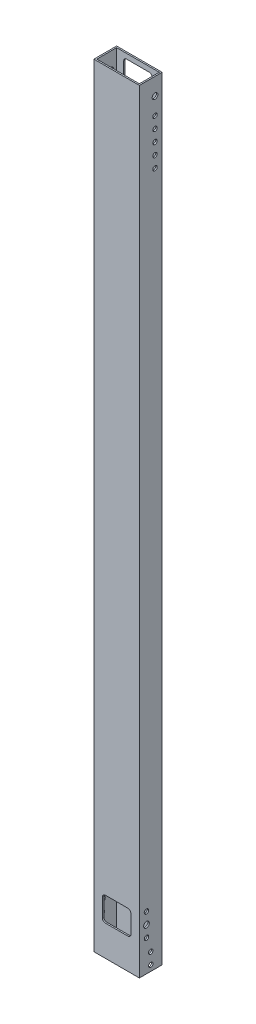
SolidWorks part; units mm, degrees
material "6061-T6 (SS)"
ref_plane "Front Plane" through (0, 0, 0) normal (0, 0, 1) x (1, 0, 0)
ref_plane "Top Plane" through (0, 0, 0) normal (0, 1, 0) x (1, 0, 0)
ref_plane "Right Plane" through (0, 0, 0) normal (1, 0, 0) x (0, 0, -1)
sketch "Sketch1" plane through (0, 0, 0) normal (0, 0, 1) x (1, 0, 0)
  line L1 (-25.4, -431.8) -> (25.4, -431.8)
  line L2 (-25.4, -431.8) -> (-25.4, 431.8)
  line L3 (-25.4, 431.8) -> (25.4, 431.8)
  line L4 (25.4, -431.8) -> (25.4, 431.8)
  line L5 (-25.4, -431.8) -> (25.4, 431.8) construction
  line L6 (-25.4, 431.8) -> (25.4, -431.8) construction
  point P0 (0, 0)
  dimension "D1" = 50.8
  dimension "D2" = 863.6
extrude "Boss-Extrude1" add sketch "Sketch1" along normal mid plane 25.4
shell "Shell1" thickness 1.5875 removed face at (0, -431.8, 0) removed face at (0, 431.8, 0)
sketch "Sketch3" plane through (0, 0, 0) normal (1, 0, 0) x (0, 0, -1)
  line L0 (-12.7, -431.8) -> (12.7, -431.8) construction
  circle A0 centre (0, -425.45) radius 2.4892
  circle A1 centre (0, -412.75) radius 2.4892
  point P6 (0, -431.8)
  dimension "D1" = 4.9784
  dimension "D2" = 6.35
  dimension "D3" = 12.7
extrude "Cut-Extrude1" cut sketch "Sketch3" against normal through all both and the other way through all
sketch "Sketch4" plane through (0, 0, 0) normal (1, 0, 0) x (0, 0, -1)
  line L4 (-12.7, -431.8) -> (12.7, -431.8) construction
  line L5 (-12.7, 431.8) -> (-12.7, -431.8) construction
  circle A3 centre (-4.7625, -384.175) radius 3.175
  circle A4 centre (-4.7625, -371.475) radius 2.4892
  circle A5 centre (-4.7625, -396.875) radius 2.4892
  dimension "D7" = 6.35
  dimension "D8" = 4.9784
  dimension "D9" = 12.7
  dimension "D10" = 12.7
  dimension "D11" = 47.625
  dimension "D12" = 7.9375
extrude "Cut-Extrude2" cut sketch "Sketch4" against normal through all both and the other way through all
sketch "Sketch5" plane through (0, 0, 0) normal (0, 0, 1) x (1, 0, 0)
  line L0 (-25.4, -431.8) -> (25.4, -431.8) construction
  line L1 (-15.875, -370.6813) -> (15.875, -370.6813)
  line L2 (-15.875, -370.6813) -> (-15.875, -397.6688)
  line L3 (-15.875, -397.6688) -> (15.875, -397.6688)
  line L4 (15.875, -370.6813) -> (15.875, -397.6688)
  point P4 (0, -397.6688)
  point P7 (0, -431.8)
  point P8 (15.875, -384.175)
  dimension "D1" = 31.75
  dimension "D2" = 26.9875
  dimension "D3" = 47.625
extrude "Cut-Extrude3" cut sketch "Sketch5" along normal through all
fillet "Fillet1" radius 3.175 4 edges at (-15.875, -397.6688, 11.9062) (15.875, -397.6688, 11.9062) (-15.875, -370.6813, 11.9062) (15.875, -370.6813, 11.9062)
sketch "Sketch6" plane through (0, 0, 0) normal (1, 0, 0) x (0, 0, -1)
  line L0 (12.7, 431.8) -> (12.7, -431.8) construction
  line L1 (-12.7, 431.8) -> (12.7, 431.8) construction
  circle A0 centre (4.7625, 412.75) radius 3.175
  dimension "D1" = 6.35
  dimension "D2" = 7.9375
  dimension "D3" = 19.05
extrude "Cut-Extrude4" cut sketch "Sketch6" against normal through all both and the other way through all
sketch "Sketch7" plane through (0, 0, 0) normal (0, 0, 1) x (1, 0, 0)
  line L0 (25.4, 431.8) -> (-25.4, 431.8) construction
  line L1 (15.875, 426.2437) -> (-15.875, 426.2437)
  line L2 (15.875, 426.2437) -> (15.875, 399.2562)
  line L3 (15.875, 399.2562) -> (-15.875, 399.2562)
  line L4 (-15.875, 426.2437) -> (-15.875, 399.2562)
  point P5 (0, 426.2437)
  point P8 (0, 431.8)
  point P9 (-15.875, 412.75)
  dimension "D1" = 26.9875
  dimension "D2" = 31.75
  dimension "D3" = 19.05
extrude "Cut-Extrude5" cut sketch "Sketch7" against normal through all
fillet "Fillet2" radius 3.175 4 edges at (15.875, 399.2562, -11.9062) (-15.875, 399.2562, -11.9062) (-15.875, 426.2437, -11.9062) (15.875, 426.2437, -11.9062)
sketch "Sketch8" plane through (0, 0, 0) normal (1, 0, 0) x (0, 0, -1)
  line L0 (12.7, 431.8) -> (12.7, -431.8) construction
  line L1 (-12.7, 431.8) -> (12.7, 431.8) construction
  circle A0 centre (4.7625, 393.7) radius 2.4892
  circle A1 centre (4.7625, 381) radius 2.4892
  circle A2 centre (4.7625, 368.3) radius 2.4892
  circle A3 centre (4.7625, 355.6) radius 2.4892
  circle A4 centre (4.7625, 342.9) radius 2.4892
  dimension "D3" = 4.9784
  dimension "D1" = 7.9375
  dimension "D2" = 38.1
  dimension "D5" = 12.7
  dimension "D4" = 5
extrude "Cut-Extrude6" cut sketch "Sketch8" against normal through all both and the other way through all
